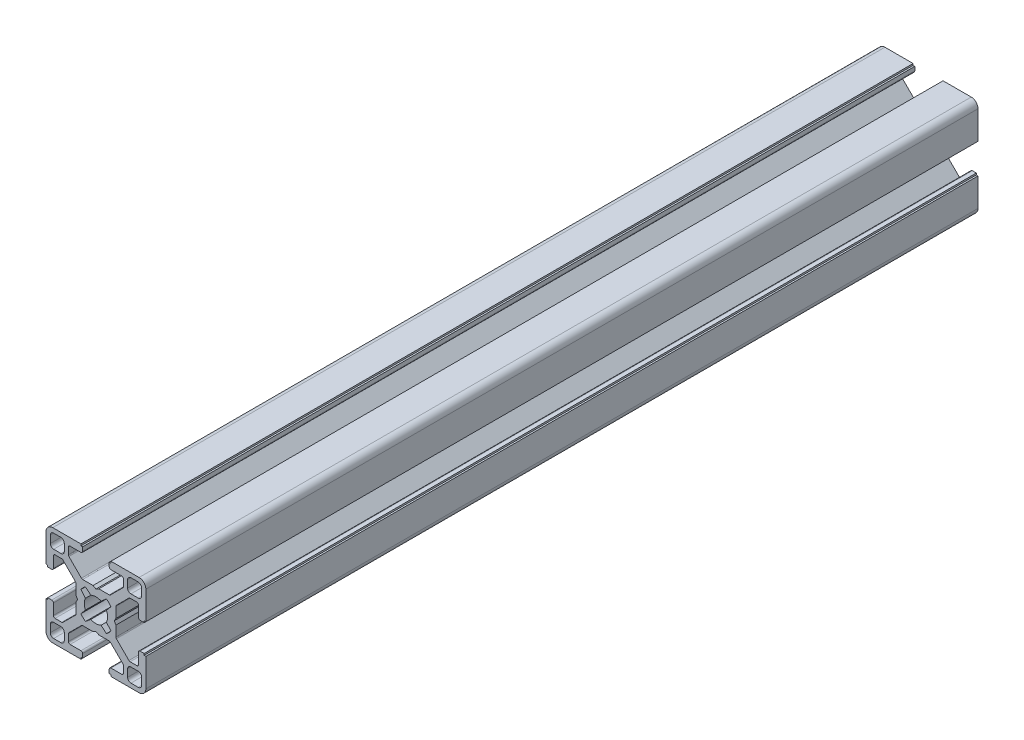
SolidWorks part; units mm, degrees
ref_plane "Front Plane" through (0, 0, 0) normal (0, 0, 1) x (1, 0, 0)
ref_plane "Top Plane" through (0, 0, 0) normal (0, 1, 0) x (1, 0, 0)
ref_plane "Right Plane" through (0, 0, 0) normal (1, 0, 0) x (0, 0, -1)
sketch "Sketch1" plane through (0, 0, 0) normal (0, 0, 1) x (1, 0, 0)
  line L0 (-15, 0) -> (15, 0) construction
  line L1 (0, -15) -> (0, 15) construction
  line L2 (-4.5, 15) -> (4.5, 15) construction
  line L3 (-4, -15) -> (4, -15) construction
  line L4 (-4.5, 15) -> (-4.5, 14.5)
  line L5 (-4.5, 14.5) -> (-4, 14.5)
  line L6 (-4, 14.5) -> (-4, 13.29)
  line L7 (-4.5, 12.79) -> (-7.7675, 12.79)
  line L8 (-8.2675, 12.29) -> (-8.2675, 10.2707)
  line L9 (-8.1211, 9.9171) -> (-4.3504, 6.1464)
  line L10 (-3.9968, 6) -> (0, 6)
  line L11 (0, 0) -> (-15, 15) construction
  line L12 (-4.5, 15) -> (-12.968, 15)
  line L14 (-12.705, 9.5135) -> (-10.5135, 9.5135)
  line L15 (-13.705, 10.5135) -> (-13.705, 12.705)
  line L16 (-12.705, 13.705) -> (-10.5135, 13.705)
  line L17 (-9.5135, 10.5135) -> (-9.5135, 12.705)
  line L18 (-13.705, 9.5135) -> (-9.5135, 13.705) construction
  line L19 (-13.705, 13.705) -> (-9.5135, 9.5135) construction
  line L20 (-3.1568, 4.5038) -> (-1.5303, 3.1477) construction
  line L21 (-4.5038, 3.1568) -> (-3.1477, 1.5303) construction
  line L22 (-6, 3.9968) -> (-6, 0)
  line L23 (-9.9171, 8.1211) -> (-6.1464, 4.3504)
  line L24 (-15, 4.5) -> (-15, 12.968)
  line L25 (-12.29, 8.2675) -> (-10.2707, 8.2675)
  line L26 (-12.79, 4.5) -> (-12.79, 7.7675)
  line L27 (-14.5, 4) -> (-13.29, 4)
  line L28 (-14.5, 4.5) -> (-14.5, 4)
  line L29 (-15, 4.5) -> (-14.5, 4.5)
  circle A0 centre (0, 0) radius 3.5
  arc A1 (-12.968, 15) -> (-15, 12.968) centre (-12.968, 12.968) ccw
  circle A2 centre (0, 0) radius 5.5 construction
  arc A3 (-10.5135, 9.5135) -> (-9.5135, 10.5135) centre (-10.5135, 10.5135) ccw
  arc A4 (-13.705, 12.705) -> (-12.705, 13.705) centre (-12.705, 12.705) cw
  arc A5 (-10.5135, 13.705) -> (-9.5135, 12.705) centre (-10.5135, 12.705) cw
  arc A6 (-12.705, 9.5135) -> (-13.705, 10.5135) centre (-12.705, 10.5135) cw
  arc A7 (-12.79, 4.5) -> (-13.29, 4) centre (-13.29, 4.5) cw
  arc A8 (-12.29, 8.2675) -> (-12.79, 7.7675) centre (-12.29, 7.7675) ccw
  arc A9 (-9.9171, 8.1211) -> (-10.2707, 8.2675) centre (-10.2707, 7.7675) ccw
  arc A10 (-6, 3.9968) -> (-6.1464, 4.3504) centre (-6.5, 3.9968) ccw
  arc A11 (-4.3504, 6.1464) -> (-3.9968, 6) centre (-3.9968, 6.5) ccw
  arc A12 (-4, 13.29) -> (-4.5, 12.79) centre (-4.5, 13.29) cw
  arc A13 (-7.7675, 12.79) -> (-8.2675, 12.29) centre (-7.7675, 12.29) ccw
  arc A14 (-8.2675, 10.2707) -> (-8.1211, 9.9171) centre (-7.7675, 10.2707) ccw
  point P4 (0, 0)
  point P8 (0, 0)
  point P13 (0, 15)
  point P15 (0, -15)
  point P16 (0, 6)
  point P23 (-11.6092, 11.6093)
  point P26 (0, 6)
  point P62 (-12.79, 4)
  point P65 (-12.79, 8.2675)
  point P68 (-10.0636, 8.2675)
  point P71 (-6, 4.2039)
  point P74 (-4.2039, 6)
  point P77 (-4, 12.79)
  point P80 (-8.2675, 12.79)
  point P83 (-8.2675, 10.0636)
  dimension "Center Hole Diameter" = 7
  dimension "D11" = 2.032
  dimension "D9" = 11
  dimension "D13" = 1
  dimension "D14" = 0.5
  dimension "Rail Height" = 30
  dimension "Rail Width" = 30
  dimension "T-Slot Width" = 8
  dimension "T-Slot Depth" = 9
  dimension "D1" = 9
  dimension "D2" = 45
  dimension "D3" = 8
  dimension "D4" = 2.21
  dimension "D5" = 16.535
  dimension "D7" = 2.54
  dimension "D6" = 1.295
  dimension "D8" = 1.246
  dimension "D10" = 10.36
  dimension "D12" = 1.905
sketch "Sketch2" plane through (0, 0, 0) normal (1, 0, 0) x (0, 0, -1)
  line L0 (-76.2, 0) -> (76.2, 0) construction
  line L2 (0, -15) -> (0, 15) construction
  line L3 (0, -15) -> (0, 15) construction
  line L4 (-76.2, -15) -> (-76.2, 15) construction
  line L5 (76.2, -15) -> (76.2, 15) construction
  point P0 (-38.7, 0)
  point P3 (0, 0)
  point P4 (38.7, 0)
  point P12 (-76.2, 0)
  point P14 (76.2, 0)
  dimension "Length" = 152.4
  dimension "D1" = 37.5
sketch "Sketch3" plane through (0, 0, 0) normal (0, 0, 1) x (1, 0, 0)
  line L0 (-4.5038, 3.1568) -> (-3.1477, 1.5303)
  line L1 (0, 3.5) -> (0, 5.5)
  line L2 (-5.5, 0) -> (-3.5, 0)
  line L7 (-6, 3.9968) -> (-6, 0) construction
  line L31 (-9.9171, 8.1211) -> (-6.1464, 4.3504) construction
  line L117 (-12.29, 8.2675) -> (-10.2707, 8.2675) construction
  line L118 (-12.79, 4.5) -> (-12.79, 7.7675) construction
  line L157 (-12.705, 9.5135) -> (-10.5135, 9.5135)
  line L158 (-9.5135, 10.5135) -> (-9.5135, 12.705)
  line L163 (-10.5135, 13.705) -> (-12.705, 13.705)
  line L164 (-13.705, 12.705) -> (-13.705, 10.5135)
  line L165 (-12.705, 9.5135) -> (-10.5135, 9.5135)
  line L166 (-9.5135, 10.5135) -> (-9.5135, 12.705)
  line L167 (-10.5135, 13.705) -> (-12.705, 13.705)
  line L168 (-13.705, 12.705) -> (-13.705, 10.5135)
  line L169 (-14.5, 4) -> (-13.29, 4) construction
  line L170 (-14.5, 4.5) -> (-14.5, 4) construction
  line L171 (-15, 4.5) -> (-14.5, 4.5) construction
  line L172 (-15, 4.5) -> (-15, 12.968) construction
  line L173 (-4.5, 15) -> (-12.968, 15) construction
  line L174 (-4.5, 15) -> (-4.5, 14.5) construction
  line L175 (-4.5, 14.5) -> (-4, 14.5) construction
  line L176 (-4, 14.5) -> (-4, 13.29) construction
  line L177 (-4.5, 12.79) -> (-7.7675, 12.79) construction
  line L178 (-8.2675, 12.29) -> (-8.2675, 10.2707) construction
  line L179 (-8.1211, 9.9171) -> (-4.3504, 6.1464) construction
  line L180 (-3.9968, 6) -> (0, 6) construction
  line L181 (-6, 3.9968) -> (-6, 0.866)
  line L182 (-9.9171, 8.1211) -> (-6.1464, 4.3504)
  line L183 (-12.29, 8.2675) -> (-10.2707, 8.2675)
  line L184 (-12.79, 4.5) -> (-12.79, 7.7675)
  line L185 (-14.5, 4) -> (-13.29, 4)
  line L186 (-14.5, 4.5) -> (-14.5, 4)
  line L187 (-15, 4.5) -> (-14.5, 4.5)
  line L188 (-15, 4.5) -> (-15, 12.968)
  line L189 (-4.5, 15) -> (-12.968, 15)
  line L190 (-4.5, 15) -> (-4.5, 14.5)
  line L191 (-4.5, 14.5) -> (-4, 14.5)
  line L192 (-4, 14.5) -> (-4, 13.29)
  line L193 (-4.5, 12.79) -> (-7.7675, 12.79)
  line L194 (-8.2675, 12.29) -> (-8.2675, 10.2707)
  line L195 (-8.1211, 9.9171) -> (-4.3504, 6.1464)
  line L196 (-3.9968, 6) -> (-0.866, 6)
  line L197 (-0.866, 6) -> (0, 5.5)
  line L198 (0, -15) -> (0, 15) construction
  line L199 (0, 0) -> (-15, 15) construction
  line L200 (0, 0) -> (-15, 15) construction
  line L201 (-3.1568, 4.5038) -> (-1.5303, 3.1477) construction
  line L202 (-3.1568, 4.5038) -> (-1.5303, 3.1477)
  line L203 (-6, 0.866) -> (-5.5, 0)
  line L204 (-15, 0) -> (15, 0) construction
  line L205 (-15, 0) -> (15, 0) construction
  line L206 (0, -15) -> (0, 15) construction
  arc A0 (-3.5, 0) -> (-3.1477, 1.5303) centre (0, 0) cw
  arc A10 (-6, 3.9968) -> (-6.1464, 4.3504) centre (-6.5, 3.9968) ccw construction
  circle A16 centre (0, 0) radius 3.5
  arc A18 (0, 3.5) -> (-1.5303, 3.1477) centre (0, 0) ccw
  arc A20 (-9.9171, 8.1211) -> (-10.2707, 8.2675) centre (-10.2707, 7.7675) ccw construction
  arc A22 (-12.29, 8.2675) -> (-12.79, 7.7675) centre (-12.29, 7.7675) ccw construction
  arc A28 (-13.29, 4) -> (-12.79, 4.5) centre (-13.29, 4.5) ccw construction
  arc A29 (-10.5135, 9.5135) -> (-9.5135, 10.5135) centre (-10.5135, 10.5135) ccw
  arc A30 (-9.5135, 12.705) -> (-10.5135, 13.705) centre (-10.5135, 12.705) ccw
  arc A31 (-12.705, 13.705) -> (-13.705, 12.705) centre (-12.705, 12.705) ccw
  arc A32 (-13.705, 10.5135) -> (-12.705, 9.5135) centre (-12.705, 10.5135) ccw
  arc A33 (-10.5135, 9.5135) -> (-9.5135, 10.5135) centre (-10.5135, 10.5135) ccw
  arc A34 (-9.5135, 12.705) -> (-10.5135, 13.705) centre (-10.5135, 12.705) ccw
  arc A35 (-12.705, 13.705) -> (-13.705, 12.705) centre (-12.705, 12.705) ccw
  arc A36 (-13.705, 10.5135) -> (-12.705, 9.5135) centre (-12.705, 10.5135) ccw
  arc A37 (-12.968, 15) -> (-15, 12.968) centre (-12.968, 12.968) ccw construction
  arc A38 (-4.5, 12.79) -> (-4, 13.29) centre (-4.5, 13.29) ccw construction
  arc A39 (-7.7675, 12.79) -> (-8.2675, 12.29) centre (-7.7675, 12.29) ccw construction
  arc A40 (-8.2675, 10.2707) -> (-8.1211, 9.9171) centre (-7.7675, 10.2707) ccw construction
  arc A41 (-4.3504, 6.1464) -> (-3.9968, 6) centre (-3.9968, 6.5) ccw construction
  arc A42 (-6, 3.9968) -> (-6.1464, 4.3504) centre (-6.5, 3.9968) ccw
  arc A43 (-9.9171, 8.1211) -> (-10.2707, 8.2675) centre (-10.2707, 7.7675) ccw
  arc A44 (-12.29, 8.2675) -> (-12.79, 7.7675) centre (-12.29, 7.7675) ccw
  arc A45 (-13.29, 4) -> (-12.79, 4.5) centre (-13.29, 4.5) ccw
  arc A46 (-12.968, 15) -> (-15, 12.968) centre (-12.968, 12.968) ccw
  arc A47 (-4.5, 12.79) -> (-4, 13.29) centre (-4.5, 13.29) ccw
  arc A48 (-7.7675, 12.79) -> (-8.2675, 12.29) centre (-7.7675, 12.29) ccw
  arc A49 (-8.2675, 10.2707) -> (-8.1211, 9.9171) centre (-7.7675, 10.2707) ccw
  arc A50 (-4.3504, 6.1464) -> (-3.9968, 6) centre (-3.9968, 6.5) ccw
  circle A51 centre (0, 0) radius 5.5 construction
  arc A52 (-3.1568, 4.5038) -> (-4.5038, 3.1568) centre (0, 0) ccw
  dimension "D3" = 60
  dimension "D4" = 60
  dimension "D1" = 0
  dimension "D2" = 0
extrude "Boss-Extrude1" add sketch "Sketch3" along normal mid plane 250
pattern_circular "CirPattern1" count 4 over 360 about axis through (0, 0, 76.2) along (0, 0, -1) of "Boss-Extrude1"
ref_plane "Contact Plane1" through (15, 0, 0) normal (1, 0, 0) x (0, 0, -1)
ref_plane "Contact Plane2" through (0, -15, 0) normal (0, 1, 0) x (1, 0, 0)
ref_plane "Contact Plane3" through (-15, 0, 0) normal (1, 0, 0) x (0, 0, -1)
ref_plane "Contact Plane4" through (0, 15, 0) normal (0, 1, 0) x (1, 0, 0)
equation "\"D1@Sketch2\" = \"Rail Height@Sketch1\" * 1.25"
equation "\"D1@Sketch1\"=\"T-Slot Width@Sketch1\"+1mm"
equation "\"D3@Sketch1\"=\"T-Slot Width@Sketch1\""
equation "\"D1@Boss-Extrude1\"=\"Length\""
equation "\"Length\" = 250mm"
